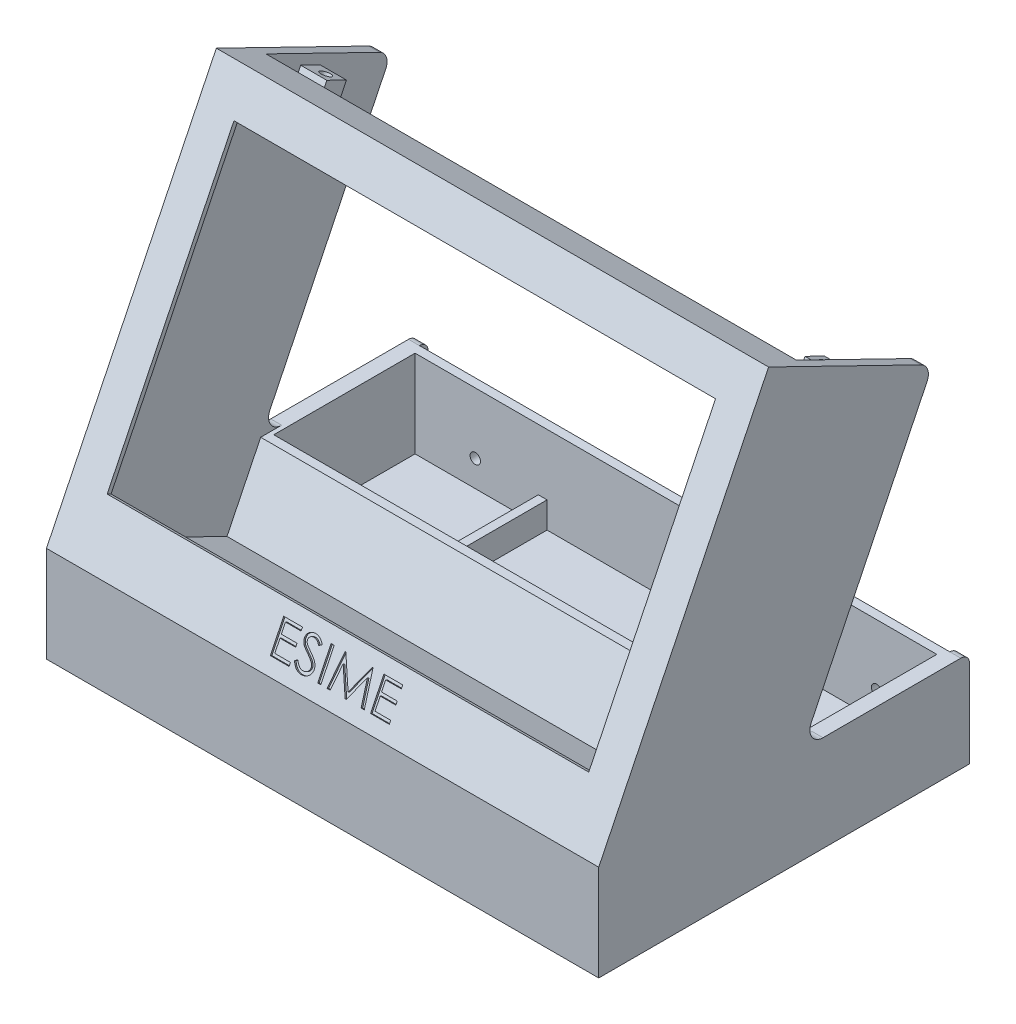
SolidWorks part; units mm, degrees
ref_plane "Alzado" through (0, 0, 0) normal (0, 0, 1) x (1, 0, 0)
ref_plane "Planta" through (0, 0, 0) normal (0, 1, 0) x (1, 0, 0)
ref_plane "Vista lateral" through (0, 0, 0) normal (1, 0, 0) x (0, 0, -1)
sketch "Croquis1" plane through (0, 0, 0) normal (1, 0, 0) x (0, 0, -1)
  line L0 (0, 0) -> (74, 0)
  line L1 (0, 0) -> (0, 22)
  line L2 (0, 22) -> (36.8232, 97.4987)
  line L3 (36.8232, 97.4987) -> (65.5846, 83.4708)
  line L4 (65.5846, 83.4708) -> (35.6033, 22)
  line L5 (35.6033, 22) -> (74, 22)
  line L6 (74, 22) -> (74, 0)
  line L7 (74, 22) -> (74, 79.3664)
  line L8 (74, 79.3664) -> (65.5846, 83.4708)
  line L9 (36.8232, 97.4987) -> (35.9464, 95.7011)
  line L10 (35.9464, 95.7011) -> (74, 77.1411)
  line L11 (72, 0) -> (72, 78.1166)
  line L12 (65.5846, 83.4708) -> (64.7078, 81.6732)
  line L13 (0, 0) -> (-11, 0)
  line L14 (-11, 0) -> (-11, 22)
  line L15 (35.9464, 95.7011) -> (27.0603, 100.0352)
  line L17 (-11, 22) -> (27.0603, 100.0352)
  line L18 (-11, 22) -> (0, 22) construction
  point P13 (72, 22)
  dimension "D1" = 32
  dimension "D2" = 64
  dimension "D3" = 84
  dimension "D4" = 22
  dimension "D5" = 74
  dimension "D6" = 2
  dimension "D7" = 2
  dimension "D8" = 11
extrude "Saliente-Extruir1" add sketch "Croquis1" against normal blind 132.6 contours L6 L5 L4 L3 L2 L1 L0 | L18 L14 L13 L1 | L17 L18 L2 region at (0, 37.6722, -34.5006) region at (0, 11, 5.5) region at (0, 59.9444, -12.9543)
sketch "Croquis2" plane through (0, 91.4734, -44.6146) normal (0, 0.8988, -0.4384) x (1, 0, 0)
  line L0 (-127.1, 22.3558) -> (-127.1, -18.5309)
  line L1 (-132.6, 22.3558) -> (0, 22.3558) construction
  line L2 (-127.1, -18.5309) -> (-5.5, -18.5309)
  line L3 (-5.5, -18.5309) -> (-5.5, 22.3558)
  line L4 (-132.6, 22.3558) -> (0, 22.3558) construction
  line L5 (-132.6, -19.5309) -> (-132.6, 22.3558) construction
  line L6 (0, -19.5309) -> (0, 22.3558) construction
  line L8 (-127.1, 22.3558) -> (-5.5, 22.3558)
  line L10 (-132.6, -19.5309) -> (0, -19.5309) construction
  dimension "D1" = 5.5
  dimension "D2" = 5.5
  dimension "D3" = 1
sketch "Croquis4" plane through (0, 22, 0) normal (0, 1, 0) x (1, 0, 0)
  line L0 (-132.6, 53.8016) -> (0, 53.8016) construction
  line L1 (-132.6, 35.6033) -> (-132.6, 72) construction
  line L2 (0, 35.6033) -> (0, 72) construction
  line L3 (-132.6, 72) -> (0, 72) construction
  line L4 (-126.1, 37.6033) -> (-6.5, 37.6033)
  line L5 (-126.1, 37.6033) -> (-126.1, 70)
  line L6 (-126.1, 70) -> (-6.5, 70)
  line L7 (-6.5, 37.6033) -> (-6.5, 70)
  line L8 (-126.1, 37.6033) -> (-6.5, 70) construction
  line L9 (-126.1, 70) -> (-6.5, 37.6033) construction
  point P6 (-66.3, 53.8016)
  dimension "D1" = 6.5
  dimension "D2" = 2
extrude "Cortar-Extruir3" cut sketch "Croquis4" against normal blind 20
extrude "Cortar-Extruir6" cut sketch "Croquis2" against normal blind 84
sketch "Croquis10" plane through (0, 8.5618, 17.5543) normal (0, 0.4384, 0.8988) x (1, 0, 0)
  line L1 (-127.1, 94.5124) -> (-5.5, 94.5124)
  line L2 (-127.1, 94.5124) -> (-127.1, 28.2124)
  line L3 (-127.1, 28.2124) -> (-5.5, 28.2124)
  line L4 (-5.5, 94.5124) -> (-5.5, 28.2124)
  line L5 (0, 14.9514) -> (0, 101.7735) construction
  line L6 (-132.6, 14.9514) -> (-132.6, 101.7735) construction
  line L8 (0, 101.7735) -> (0, 14.9514) construction
  point P10 (0, 58.3624)
  point P11 (-5.5, 61.3624)
  dimension "D1" = 3
  dimension "D2" = 5.5
  dimension "D3" = 5.5
  dimension "D4" = 66.3
extrude "Cortar-Extruir7" cut sketch "Croquis10" against normal blind 40
sketch "Croquis11" plane through (0, 0, -72) normal (0, 0, -1) x (-1, 0, 0)
  line L0 (5.5, 22) -> (5.5, 0)
  line L1 (132.6, 0) -> (0, 0) construction
  line L2 (66.3, 0) -> (66.3, 22) construction
  line L3 (5.5, 22) -> (0, 22)
  line L4 (5.5, 22) -> (5.5, 0)
  line L5 (5.5, 0) -> (0, 0)
  line L6 (0, 22) -> (0, 0)
  line L7 (132.6, 22) -> (0, 22) construction
  line L8 (127.1, 0) -> (132.6, 0)
  line L9 (132.6, 22) -> (132.6, 0)
  line L10 (127.1, 22) -> (132.6, 22)
  line L11 (127.1, 22) -> (127.1, 0)
  line L12 (127.1, 22) -> (127.1, 0)
  line M7 (0, 22) -> (0, 0)
  line M8 (0, 0) -> (132.6, 0)
  line M9 (132.6, 0) -> (132.6, 22)
  line M10 (132.6, 22) -> (0, 22)
extrude "Saliente-Extruir3" add sketch "Croquis11" along normal blind 2 contours L0 M10 M7 M8 | L11 M10 M8 M9 region at (-2.75, 11, -72) region at (-129.85, 11, -72)
sketch "Croquis12" plane through (0, 91.4734, -44.6146) normal (0, 0.8988, -0.4384) x (1, 0, 0)
  line L0 (-5.5, -18.5309) -> (-5.5, -9.6409) construction
  line L1 (-5.5, -18.5309) -> (-5.5, 22.3558) construction
  line L2 (-5.5, -9.6409) -> (-127.1, -9.6409)
  line L3 (-127.1, 22.3558) -> (-127.1, -18.5309) construction
  line L4 (-127.1, -9.6409) -> (-127.1, 22.3558)
  line L5 (-127.1, 22.3558) -> (-132.6, 22.3558)
  line L6 (-132.6, 22.3558) -> (-132.6, -19.5309)
  line L7 (-132.6, -19.5309) -> (0, -19.5309)
  line L8 (0, -19.5309) -> (0, 22.3558) construction
  line L9 (0, -19.5309) -> (0, 22.3558)
  line L10 (0, 22.3558) -> (-5.5, 22.3558)
  line L11 (-5.5, 22.3558) -> (-5.5, -9.6409)
  dimension "D1" = 8.89
extrude "Saliente-Extruir4" add sketch "Croquis12" along normal blind 2
sketch "Croquis13" plane through (0, 0, -72) normal (0, 0, -1) x (-1, 0, 0)
  line L0 (5.5, 22) -> (5.5, 0) construction
  line L1 (127.1, 0) -> (5.5, 0) construction
  line L2 (66.3, 0) -> (66.3, 22) construction
  line L3 (127.1, 22) -> (5.5, 22) construction
  circle A0 centre (20.3, 8) radius 1.2
  circle A1 centre (112.3, 8) radius 1.2
  dimension "D3" = 2.4
  dimension "D1" = 14.8
  dimension "D2" = 8
extrude "Cortar-Extruir9" cut sketch "Croquis13" against normal up to next
sketch "Croquis21" plane through (0, 2, 0) normal (0, 1, 0) x (1, 0, 0)
  line L0 (-66.3, 37.6033) -> (-66.3, 70) construction
  line L1 (-126.1, 37.6033) -> (-6.5, 37.6033) construction
  line L2 (-6.5, 70) -> (-126.1, 70) construction
  line L3 (-95.85, 53.8016) -> (-36.75, 53.8016) construction
  line L4 (-95.85, 37.6033) -> (-95.85, 70)
  line L5 (-36.75, 37.6033) -> (-36.75, 70)
  line L6 (-97.85, 102.3967) -> (-97.85, 37.6033)
  line L7 (-97.85, 70) -> (-95.85, 70)
  line L8 (-95.85, 37.6033) -> (-97.85, 37.6033)
  line L9 (-34.75, 70) -> (-36.75, 70)
  line L10 (-34.75, 102.3967) -> (-34.75, 37.6033)
  line L11 (-36.75, 37.6033) -> (-36.75, 70)
  line L12 (-36.75, 37.6033) -> (-34.75, 37.6033)
  point P9 (-66.3, 53.8016)
  point P11 (-95.85, 53.8016)
  point P15 (-36.75, 53.8016)
  point P18 (-97.85, 70)
  line M8 (-6.5, 70) -> (-126.1, 70)
  line M10 (-126.1, 37.6033) -> (-6.5, 37.6033)
  dimension "D1" = 59.1
  dimension "D2" = 2
extrude "Saliente-Extruir10" add sketch "Croquis21" along normal blind 6 contours L6 L4 M8 M10 | L10 L5 M8 M10 region at (-96.85, 2, -53.8016) region at (-35.75, 2, -53.8016)
sketch "Croquis22" plane through (0, 93.271, -45.4913) normal (0, 0.8988, -0.4384) x (1, 0, 0)
  line L0 (0, -19.5309) -> (0, 22.3558) construction
  line L1 (-132.6, -19.5309) -> (0, -19.5309) construction
  line L2 (-66.3, -19.5309) -> (-66.3, 32.9208) construction
  line L3 (-95.85, 32.9208) -> (-36.75, 32.9208) construction
  line L4 (-9, 2.7191) -> (-5.5, 2.7191) construction
  line L5 (-5.5, 22.3558) -> (-5.5, -9.6409) construction
  line L6 (-5.5, 0.2191) -> (-5.5, 5.2191)
  line L7 (-5.5, -18.5309) -> (-5.5, 22.3558) construction
  line L8 (-5.5, 5.2191) -> (-11.5, 5.2191)
  line L9 (-11.5, 5.2191) -> (-11.5, 0.2191)
  line L10 (-11.5, 0.2191) -> (-5.5, 0.2191)
  line L11 (-121.1, 5.2191) -> (-121.1, 0.2191)
  line L12 (-127.1, 5.2191) -> (-121.1, 5.2191)
  line L13 (-127.1, 0.2191) -> (-127.1, 5.2191)
  line L14 (-121.1, 0.2191) -> (-127.1, 0.2191)
  circle A0 centre (-9, 2.7191) radius 1.2
  circle A1 centre (-123.6, 2.7191) radius 1.2
  point P18 (-5.5, 2.7191)
  dimension "D3" = 2.4
  dimension "D1" = 9
  dimension "D2" = 22.25
  dimension "D4" = 5
  dimension "D5" = 6
extrude "Saliente-Extruir11" add sketch "Croquis22" against normal blind 5
extrude "Cortar-Extruir12" cut sketch "Croquis22<2>" against normal blind 2.1
sketch "Croquis22<2>" plane through (0, 93.271, -45.4913) normal (0, 0.8988, -0.4384) x (1, 0, 0) same geometry as "Croquis22"
sketch "Croquis23" plane through (0, 8.5618, 17.5543) normal (0, 0.4384, 0.8988) x (1, 0, 0)
  line L0 (-127.1, 28.2124) -> (-5.5, 28.2124) construction
  line L3 (-81.3, 18.2124) -> (-51.3, 18.2124) construction
  text T0 "ESIME" font "Century Gothic" height 7
  point P9 (-66.3, 18.2124)
  dimension "D1" = 10
  dimension "D2" = 30
extrude "Cortar-Extruir13" cut sketch "Croquis23" against normal blind 0.4
sketch "Croquis25" plane through (-127.1, 0, 0) normal (1, 0, 0) x (0, 0, -1)
  line L0 (-5.1867, 33.9189) -> (23.8773, 93.509)
  line L1 (23.8773, 93.509) -> (24.7761, 93.0706)
  line L2 (24.7761, 93.0706) -> (-4.2879, 33.4806)
  line L3 (-4.2879, 33.4806) -> (-5.1867, 33.9189)
extrude "Saliente-Extruir12" add sketch "Croquis25" along normal blind 5.6
extrude "Saliente-Extruir13" add sketch "Croquis25<2>" against normal blind 5.6 from surface starting at face at (-5.5, 62.0469, -23.6474)
sketch "Croquis25<2>" plane through (-127.1, 0, 0) normal (1, 0, 0) x (0, 0, -1) same geometry as "Croquis25"
ref_plane "Plano3" through (-123.6, 0, 0) normal (1, 0, 0) x (0, 0, -1)
sketch "Croquis27" plane through (-123.6, 0, 0) normal (1, 0, 0) x (0, 0, -1)
  line L0 (35.9494, 95.6997) -> (27.9591, 99.5968) construction
  line L1 (-8.8641, 24.0981) -> (27.9591, 99.5968) construction
  line L2 (35.9494, 95.6997) -> (27.9591, 99.5968)
  line L3 (-8.8641, 24.0981) -> (27.9591, 99.5968)
  line L4 (27.9591, 99.5968) -> (26.2056, 96.0016) construction
  line L5 (26.2056, 96.0016) -> (35.3978, 91.5183)
  line L6 (36.9321, 94.6641) -> (39.4487, 93.4366)
  line L7 (39.4487, 93.4366) -> (36.9062, 88.2236)
  line L8 (33.8635, 88.3725) -> (36.9321, 94.6641)
  line L9 (33.8635, 88.3725) -> (39.9033, 2)
  line L10 (70, 2) -> (37.6033, 2) construction
  line L11 (36.9062, 88.2236) -> (42.7397, 4.8)
  line L12 (39.9033, 2) -> (47.9033, 2)
  line L13 (47.9033, 2) -> (47.9033, 4.8)
  line L14 (47.9033, 4.8) -> (42.7397, 4.8)
  point P11 (35.3978, 91.5183)
  dimension "D1" = 4
  dimension "D2" = 7
  dimension "D3" = 2.8
  dimension "D4" = 94
  dimension "D5" = 8
  dimension "D6" = 2.8
  dimension "D7" = 5.8
  dimension "D8" = 2.3
sketch "Croquis28" plane through (0, 2, 0) normal (0, 1, 0) x (1, 0, 0)
  line L0 (-123.6, 45.3712) -> (-126.1, 45.3712) construction
  line L1 (-123.6, 39.9033) -> (-123.6, 47.9033) construction
  line L2 (-126.1, 70) -> (-126.1, 37.6033) construction
  line L3 (-66.3, 37.6033) -> (-66.3, 73.3761) construction
  line L4 (-95.85, 37.6033) -> (-36.75, 37.6033) construction
  circle A0 centre (-123.6, 45.3712) radius 2.25
  circle A1 centre (-9, 45.3712) radius 2.25
  dimension "D1" = 4.5
extrude "Cortar-Extruir14" cut sketch "Croquis28" against normal up to next
ref_plane "Plano4" through (0, 18, 0) normal (0, 1, 0) x (1, 0, 0)
fillet "Redondeo5" radius 3 4 edges at (-2.75, 22, -35.6033) (-129.85, 22, -35.6033) (-129.85, 83.4708, -65.5846) (-2.75, 83.4708, -65.5846)
fillet "Redondeo6" radius 2 2 edges at (-2.75, 22, -74) (-129.85, 22, -74)
fillet "Redondeo7" radius 3 2 edges at (-127.1, 87.585, -45.7434) (-5.5, 87.585, -45.7434)
ref_plane "Plano5" through (-15.5, 0, 0) normal (-1, 0, 0) x (0, 0, 1)
sketch "Croquis33" plane through (-15.5, 0, 0) normal (-1, 0, 0) x (0, 0, 1)
  line L1 (8.8641, 24.0981) -> (-27.9591, 99.5968) construction
  line L2 (-27.9591, 99.5968) -> (-35.9494, 95.6997) construction
  line L3 (-25.5793, 94.7175) -> (-26.0251, 95.6316)
  line L4 (-26.0251, 95.6316) -> (-30.7239, 98.2483)
  line L6 (-30.7239, 98.2483) -> (-33.148, 97.066)
  line L7 (-33.148, 97.066) -> (-25.5793, 94.7175)
extrude "Saliente-Extruir15" add sketch "Croquis33" along normal blind 2 contours L6 L7 L3 L4
pattern_linear "MatrizL1" count 5 spacing 25 along (-1, 0, 0) of "Saliente-Extruir15"
sketch "Croquis34" plane through (0, 0, 11) normal (0, 0, 1) x (1, 0, 0)
  line L0 (-132.6, 101.8328) -> (0, 101.8328) construction
  line L1 (-132.6, 0) -> (-129.6, 0)
  line L2 (-132.6, 0) -> (-132.6, 101.8328)
  line L3 (-132.6, 101.8328) -> (-129.6, 101.8328)
  line L4 (-129.6, 0) -> (-129.6, 101.8328)
  line L5 (-132.6, 0) -> (0, 0) construction
  line L6 (0, 101.8328) -> (-3, 101.8328)
  line L7 (0, 101.8328) -> (0, 0)
  line L8 (0, 0) -> (-3, 0)
  line L9 (-3, 101.8328) -> (-3, 0)
  dimension "D1" = 3
  dimension "D2" = 3
extrude "Cortar-Extruir16" cut sketch "Croquis34" against normal through all
sketch "Croquis35" plane through (0, 15.9747, -7.7914) normal (0, 0.8988, -0.4384) x (1, 0, 0)
  line L0 (-66.3, 22.3558) -> (-66.3, 8.3558) construction
  line L1 (-5.5, 22.3558) -> (-127.1, 22.3558) construction
  circle A0 centre (-66.3, 8.3558) radius 1.45
  dimension "D2" = 2.9
  dimension "D1" = 14
extrude "Cortar-Extruir17" cut sketch "Croquis35" against normal blind 4 contours A0
equation "\"59.|0mm\"=59"
